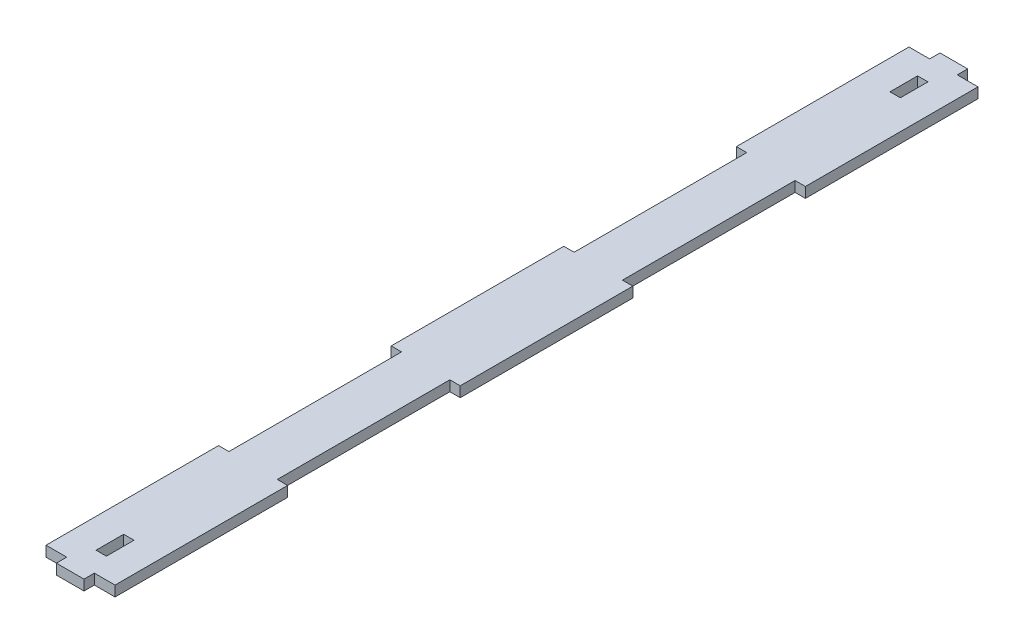
SolidWorks part; units mm, degrees
ref_plane "Alzado" through (0, 0, 0) normal (0, 0, 1) x (1, 0, 0)
ref_plane "Planta" through (0, 0, 0) normal (0, 1, 0) x (1, 0, 0)
ref_plane "Vista lateral" through (0, 0, 0) normal (1, 0, 0) x (0, 0, -1)
sketch "Croquis1" plane through (0, 0, 0) normal (0, 1, 0) x (1, 0, 0)
  line L0 (14, 250) -> (20, 250)
  line L1 (20, 100) -> (20, 150)
  line L2 (0, 0) -> (6, 0)
  line L3 (0, 150) -> (0, 100)
  line L4 (20, 125) -> (20, 150)
  line L5 (20, 150) -> (17, 150)
  line L6 (17, 150) -> (17, 200)
  line L7 (17, 200) -> (20, 200)
  line L8 (20, 200) -> (20, 250)
  line L9 (0, 250) -> (0, 200)
  line L11 (20, 200) -> (20, 250)
  line L12 (14, 0) -> (20, 0)
  line L13 (3, 200) -> (3, 150)
  line L14 (17, 50) -> (20, 50)
  line L15 (17, 100) -> (17, 50)
  line L16 (20, 100) -> (17, 100)
  line L17 (3, 150) -> (0, 150)
  line L18 (10, 253) -> (10, 240)
  line L19 (0, 200) -> (3, 200)
  line L20 (0, 100) -> (3, 100)
  line L21 (3, 250) -> (0, 250)
  line L22 (3, 100) -> (3, 50)
  line L23 (3, 50) -> (0, 50)
  line L24 (0, 50) -> (0, 0)
  line L25 (11.5, 6) -> (10, 6)
  line L26 (11.5, 14) -> (11.5, 6)
  line L27 (20, 50) -> (20, 0)
  line L28 (10, 253) -> (6, 253)
  line L29 (8.5, 14) -> (11.5, 14)
  line L30 (8.5, 6) -> (8.5, 14)
  line L31 (10, 6) -> (8.5, 6)
  line L32 (6, 253) -> (6, 250)
  line L33 (14, -3) -> (6, -3)
  line L34 (6, -3) -> (6, 0)
  line L35 (14, -3) -> (14, 0)
  line L36 (10, 10) -> (10, 6)
  line L37 (10, 253) -> (14, 253)
  line L38 (14, 253) -> (14, 250)
  line L39 (6, 250) -> (3, 250)
  line L40 (10, 240) -> (10, 244)
  line L41 (10, 244) -> (8.5, 244)
  line L42 (8.5, 244) -> (8.5, 236)
  line L43 (8.5, 236) -> (11.5, 236)
  line L44 (11.5, 236) -> (11.5, 244)
  line L45 (11.5, 244) -> (10, 244)
  line L46 (10, -3) -> (10, 10)
  dimension "D2" = 50
  dimension "D4" = 13
  dimension "D5" = 3
  dimension "D6" = 50
  dimension "D7" = 50
  dimension "D8" = 3
  dimension "D9" = 4
  dimension "D10" = 1.5
  dimension "D11" = 8
  dimension "D12" = 3
extrude "Saliente-Extruir1" add sketch "Croquis1" along normal blind 3 contours L45 L44 L43 L42 L41 L28 L32 L39 L21 L9 L19 L13 L17 L3 L20 L22 L23 L24 L34 L33 L35 L27 L14 L15 L16 L1 L5 L6 L7 L8 L38 L37 region at (10, 0, -125)
